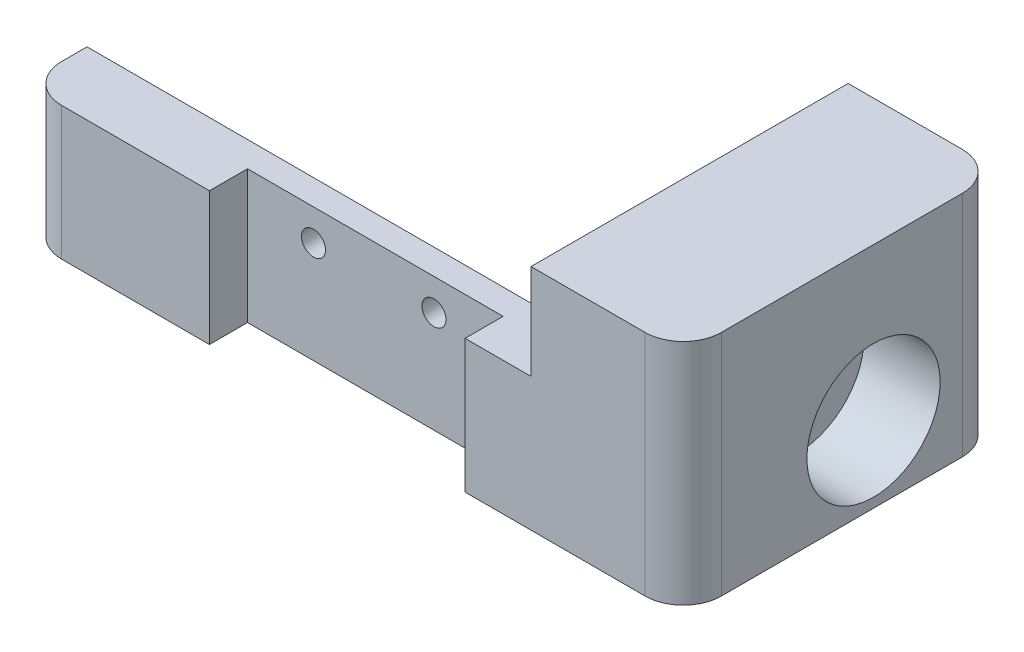
SolidWorks part; units mm, degrees
ref_plane "Front Plane" through (0, 0, 0) normal (0, 0, 1) x (1, 0, 0)
ref_plane "Top Plane" through (0, 0, 0) normal (0, 1, 0) x (1, 0, 0)
ref_plane "Right Plane" through (0, 0, 0) normal (1, 0, 0) x (0, 0, -1)
sketch "Sketch1" plane through (0, 0, 0) normal (0, 0, 1) x (1, 0, 0)
  line L1 (0, 0) -> (-40, 0)
  line L2 (0, 0) -> (0, 10.5)
  line L3 (0, 10.5) -> (-40, 10.5)
  line L4 (-40, 0) -> (-40, 10.5)
  dimension "D1" = 40
  dimension "D2" = 10.5
extrude "Boss-Extrude1" add sketch "Sketch1" along normal blind 2
sketch "Sketch2" plane through (0, 0, 2) normal (0, 0, 1) x (1, 0, 0)
  line L0 (-40, 0) -> (0, 0) construction
  line L1 (-40, 10.5) -> (-25.35, 10.5)
  line L2 (-40, 10.5) -> (-40, 0)
  line L3 (-40, 0) -> (-25.35, 0)
  line L4 (-25.35, 10.5) -> (-25.35, 0)
  line L6 (0, 10.5) -> (-5.2, 10.5)
  line L7 (0, 10.5) -> (0, 0)
  line L8 (0, 0) -> (-5.2, 0)
  line L9 (-5.2, 10.5) -> (-5.2, 0)
  dimension "D1" = 5.2
  dimension "D2" = 14.65
  dimension "D3" = 20.15
extrude "Boss-Extrude2" add sketch "Sketch2" along normal blind 3
sketch "Sketch3" plane through (0, 0, 0) normal (1, 0, 0) x (0, 0, -1)
  line L0 (0, 10.5) -> (0, 0) construction
  line L1 (-5, 18) -> (20, 18)
  line L2 (-5, 18) -> (-5, 0)
  line L3 (-5, 0) -> (20, 0)
  line L4 (20, 18) -> (20, 0)
  line L5 (-5, 0) -> (0, 0) construction
  line L6 (10, 12) -> (10, 0) construction
  line L7 (-5, 0) -> (-5, 10.5) construction
  line L8 (-5, 10.5) -> (0, 10.5) construction
  dimension "D1" = 20
  dimension "D2" = 10
  dimension "D3" = 10.5
  dimension "D4" = 18
extrude "Boss-Extrude3" add sketch "Sketch3" along normal blind 12
hole_wizard "CBORE for M5 SHCS1" positions "Sketch5" profile "Sketch4" counterbore size "M5" standard "ANSI Metric" end condition up to next
sketch "Sketch5" plane through (12, 0, 0) normal (1, 0, 0) x (0, 0, -1)
  line L0 (10, 12) -> (10, 0) construction
  point P0 (10, 6)
sketch "Sketch4" plane through (12, 6, -10) normal (0, 1, 0) x (0, 0, -1)
  line L0 (0, 0) -> (0, 12)
  line L1 (0, 12) -> (2.75, 12)
  line L3 (2.75, 12) -> (2.75, 6)
  line L4 (2.75, 6) -> (5.25, 6)
  line L5 (5.25, 6) -> (5.25, 0)
  line L7 (5.25, 0) -> (0, 0)
  line L11 (0, -6.35) -> (0, 107.95) construction
  dimension "Thru Hole Dia." = 5.5
  dimension "Thru Hole Depth" = 12
  dimension "C'Bore Dia." = 10.5
  dimension "C'Bore Depth" = 6
fillet "Fillet1" radius 3 3 edges at (-40, 5.25, 5) (12, 9, 5) (12, 9, -20)
sketch "Sketch6" plane through (0, 0, 2) normal (0, 0, 1) x (1, 0, 0)
  circle A0 centre (-20.15, 8.0227) radius 0.95
  circle A1 centre (-10.65, 8.0227) radius 0.95
  dimension "D1" = 1.9
extrude "Cut-Extrude1" cut sketch "Sketch6" against normal through all
